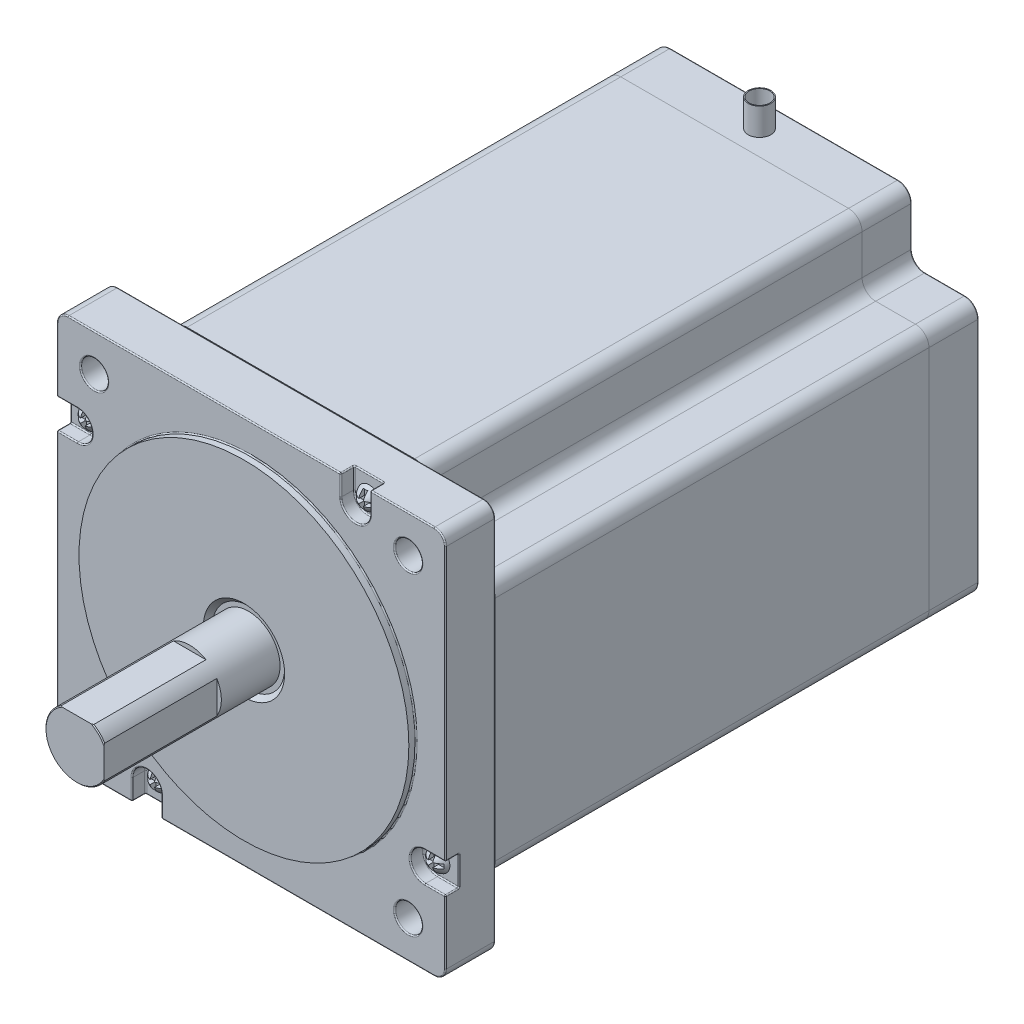
SolidWorks part; units mm, degrees
ref_plane "Front Plane" through (0, 0, 0) normal (0, 0, 1) x (1, 0, 0)
ref_plane "Top Plane" through (0, 0, 0) normal (0, 1, 0) x (1, 0, 0)
ref_plane "Right Plane" through (0, 0, 0) normal (1, 0, 0) x (0, 0, -1)
sketch "Sketch1" plane through (0, 0, 0) normal (0, 0, 1) x (1, 0, 0)
  line L0 (-43, 28.2) -> (-28.2, 28.2)
  line L1 (-28.2, 43) -> (28.2, 43)
  line L2 (-43, 28.2) -> (-43, -28.2)
  line L3 (-28.2, -43) -> (28.2, -43)
  line L4 (43, 28.2) -> (43, -28.2)
  line L7 (-28.2, 28.2) -> (-28.2, 43)
  line L8 (28.2, 43) -> (28.2, 28.2)
  line L9 (28.2, 28.2) -> (43, 28.2)
  line L10 (43, -28.2) -> (28.2, -28.2)
  line L11 (28.2, -28.2) -> (28.2, -43)
  line L12 (-28.2, -43) -> (-28.2, -28.2)
  line L13 (-28.2, -28.2) -> (-43, -28.2)
  line L14 (0, -40.6029) -> (0, 56.0394) construction
  line L15 (-73.473, 0) -> (63.7944, 0) construction
  circle A0 centre (-38.44, 23.1) radius 1.25
  circle A1 centre (0, 0) radius 8.1575 construction
  circle A2 centre (23.1, 38.44) radius 1.25
  circle A3 centre (38.44, -23.1) radius 1.25
  circle A4 centre (-23.1, -38.44) radius 1.25
  point P0 (0, 0)
  point P32 (0, 0)
  dimension "D3" = 2.5
  dimension "D4" = 4.56
  dimension "D5" = 19.9
  dimension "D6" = 4
  dimension "D1" = 43
  dimension "D2" = 86
  dimension "D7" = 43
  dimension "D8" = 14.8
  dimension "D9" = 14.8
extrude "Boss-Extrude1" add sketch "Sketch1" along normal mid plane 96
fillet "Fillet1" radius 3 12 edges at (43, -28.2, 0) (28.2, -28.2, 0) (28.2, -43, 0) (-28.2, -43, 0) (-28.2, -28.2, 0) (-43, -28.2, 0) (-43, 28.2, 0) (-28.2, 28.2, 0) (-28.2, 43, 0) (43, 28.2, 0) (28.2, 28.2, 0) (28.2, 43, 0)
sketch "Sketch2" plane through (0, 0, -48) normal (0, 0, -1) x (-1, 0, 0)
  line L12 (-43, 25.2) -> (-43, -25.2)
  line L13 (-40, -28.2) -> (-31.2, -28.2)
  line L14 (-28.2, -31.2) -> (-28.2, -40)
  line L15 (-25.2, -43) -> (25.2, -43)
  line L16 (28.2, -40) -> (28.2, -31.2)
  line L17 (31.2, -28.2) -> (40, -28.2)
  line L18 (43, -25.2) -> (43, 25.2)
  line L19 (40, 28.2) -> (31.2, 28.2)
  line L20 (28.2, 31.2) -> (28.2, 40)
  line L21 (25.2, 43) -> (-25.2, 43)
  line L22 (-28.2, 40) -> (-28.2, 31.2)
  line L23 (-31.2, 28.2) -> (-40, 28.2)
  line L24 (-43, 25.2) -> (-43, -25.2)
  line L25 (-40, -28.2) -> (-31.2, -28.2)
  line L26 (-28.2, -31.2) -> (-28.2, -40)
  line L27 (-25.2, -43) -> (25.2, -43)
  line L28 (28.2, -40) -> (28.2, -31.2)
  line L29 (31.2, -28.2) -> (40, -28.2)
  line L30 (43, -25.2) -> (43, 25.2)
  line L31 (40, 28.2) -> (31.2, 28.2)
  line L32 (28.2, 31.2) -> (28.2, 40)
  line L33 (25.2, 43) -> (-25.2, 43)
  line L34 (-28.2, 40) -> (-28.2, 31.2)
  line L35 (-31.2, 28.2) -> (-40, 28.2)
  circle A0 centre (38.44, 23.1) radius 1.25 construction
  circle A1 centre (-23.1, 38.44) radius 1.25 construction
  circle A2 centre (-38.44, -23.1) radius 1.25 construction
  circle A3 centre (23.1, -38.44) radius 1.25 construction
  circle A4 centre (38.44, 23.1) radius 1.25
  circle A5 centre (23.1, -38.44) radius 1.25
  circle A6 centre (-38.44, -23.1) radius 1.25
  circle A7 centre (-23.1, 38.44) radius 1.25
  arc A20 (-43, -25.2) -> (-40, -28.2) centre (-40, -25.2) ccw
  arc A21 (-28.2, -31.2) -> (-31.2, -28.2) centre (-31.2, -31.2) ccw
  arc A22 (-28.2, -40) -> (-25.2, -43) centre (-25.2, -40) ccw
  arc A23 (25.2, -43) -> (28.2, -40) centre (25.2, -40) ccw
  arc A24 (31.2, -28.2) -> (28.2, -31.2) centre (31.2, -31.2) ccw
  arc A25 (40, -28.2) -> (43, -25.2) centre (40, -25.2) ccw
  arc A26 (43, 25.2) -> (40, 28.2) centre (40, 25.2) ccw
  arc A27 (28.2, 31.2) -> (31.2, 28.2) centre (31.2, 31.2) ccw
  arc A28 (28.2, 40) -> (25.2, 43) centre (25.2, 40) ccw
  arc A29 (-25.2, 43) -> (-28.2, 40) centre (-25.2, 40) ccw
  arc A30 (-31.2, 28.2) -> (-28.2, 31.2) centre (-31.2, 31.2) ccw
  arc A31 (-40, 28.2) -> (-43, 25.2) centre (-40, 25.2) ccw
  arc A32 (-43, -25.2) -> (-40, -28.2) centre (-40, -25.2) ccw
  arc A33 (-28.2, -31.2) -> (-31.2, -28.2) centre (-31.2, -31.2) ccw
  arc A34 (-28.2, -40) -> (-25.2, -43) centre (-25.2, -40) ccw
  arc A35 (25.2, -43) -> (28.2, -40) centre (25.2, -40) ccw
  arc A36 (31.2, -28.2) -> (28.2, -31.2) centre (31.2, -31.2) ccw
  arc A37 (40, -28.2) -> (43, -25.2) centre (40, -25.2) ccw
  arc A38 (43, 25.2) -> (40, 28.2) centre (40, 25.2) ccw
  arc A39 (28.2, 31.2) -> (31.2, 28.2) centre (31.2, 31.2) ccw
  arc A40 (28.2, 40) -> (25.2, 43) centre (25.2, 40) ccw
  arc A41 (-25.2, 43) -> (-28.2, 40) centre (-25.2, 40) ccw
  arc A42 (-31.2, 28.2) -> (-28.2, 31.2) centre (-31.2, 31.2) ccw
  arc A43 (-40, 28.2) -> (-43, 25.2) centre (-40, 25.2) ccw
  dimension "D1" = 0
extrude "Boss-Extrude2" add sketch "Sketch2" along normal blind 11 separate body
sketch "Sketch4" plane through (0, 0, 48) normal (0, 0, 1) x (1, 0, 0)
  line L1 (-43, 43) -> (43, 43)
  line L2 (-43, 43) -> (-43, -43)
  line L3 (-43, -43) -> (43, -43)
  line L4 (43, 43) -> (43, -43)
  line L5 (-43, 43) -> (43, -43) construction
  line L6 (-43, -43) -> (43, 43) construction
  circle A0 centre (-23.1, -38.44) radius 1.25 construction
  circle A1 centre (38.44, -23.1) radius 1.25 construction
  circle A2 centre (23.1, 38.44) radius 1.25 construction
  circle A3 centre (-38.44, 23.1) radius 1.25 construction
  circle A4 centre (-23.1, -38.44) radius 1.25
  circle A5 centre (38.44, -23.1) radius 1.25
  circle A6 centre (23.1, 38.44) radius 1.25
  circle A7 centre (-38.44, 23.1) radius 1.25
  point P0 (0, 0)
  dimension "D1" = 86
  dimension "D2" = 86
extrude "Boss-Extrude3" add sketch "Sketch4" along normal blind 11 separate body
fillet "Fillet2" radius 2.5 4 edges at (-43, -43, 53.5) (43, -43, 53.5) (43, 43, 53.5) (-43, 43, 53.5)
sketch "Sketch5" plane through (0, 0, 59) normal (0, 0, 1) x (1, 0, 0)
  line L0 (-38.44, 26.35) -> (-43, 26.35)
  line L1 (-43, 40.5) -> (-43, -40.5) construction
  line L2 (-43, 26.35) -> (-43, 19.85)
  line L3 (-43, 19.85) -> (-38.44, 19.85)
  line L4 (26.35, 38.44) -> (26.35, 43)
  line L5 (26.35, 43) -> (19.85, 43)
  line L6 (19.85, 43) -> (19.85, 38.44)
  line L7 (38.44, -26.35) -> (43, -26.35)
  line L8 (43, -26.35) -> (43, -19.85)
  line L9 (43, -19.85) -> (38.44, -19.85)
  line L10 (-26.35, -38.44) -> (-26.35, -43)
  line L11 (-26.35, -43) -> (-19.85, -43)
  line L12 (-19.85, -43) -> (-19.85, -38.44)
  arc A0 (-38.44, 19.85) -> (-38.44, 26.35) centre (-38.44, 23.1) ccw
  circle A1 centre (0, 0) radius 8.2773 construction
  arc A2 (19.85, 38.44) -> (26.35, 38.44) centre (23.1, 38.44) ccw
  circle A3 centre (0, 0) radius 8.2773 construction
  arc A4 (38.44, -19.85) -> (38.44, -26.35) centre (38.44, -23.1) ccw
  circle A5 centre (0, 0) radius 8.2773 construction
  arc A6 (-19.85, -38.44) -> (-26.35, -38.44) centre (-23.1, -38.44) ccw
  circle A7 centre (0, 0) radius 8.2773 construction
  point P32 (0, 0)
  dimension "D1" = 6.5
  dimension "D2" = 4
extrude "Cut-Extrude1" cut sketch "Sketch5" against normal blind 3
sketch "Sketch6" plane through (0, 0, 59) normal (0, 0, 1) x (1, 0, 0)
  line L2 (0, 0) -> (0, 46.7465) construction
  line L3 (0, 0) -> (-44.6638, 0) construction
  circle A0 centre (-34.75, 34.75) radius 3
  circle A1 centre (0, 0) radius 7.1558 construction
  circle A2 centre (34.75, 34.75) radius 3
  circle A3 centre (0, 0) radius 7.1558 construction
  circle A4 centre (34.75, -34.75) radius 3
  circle A5 centre (0, 0) radius 7.1558 construction
  circle A6 centre (-34.75, -34.75) radius 3
  circle A7 centre (0, 0) radius 7.1558 construction
  point P20 (0, 0)
  dimension "D1" = 6
  dimension "D3" = 34.75
  dimension "D2" = 34.75
  dimension "D4" = 4
extrude "Cut-Extrude2" cut sketch "Sketch6" against normal up to surface (11 mm away) up to face at (0, 0, 48)
sketch "Sketch7" plane through (0, 0, 59) normal (0, 0, 1) x (1, 0, 0)
  circle A0 centre (0, 0) radius 36.5
  dimension "D1" = 73
extrude "Boss-Extrude4" add sketch "Sketch7" along normal blind 1.6
sketch "Sketch8" plane through (0, 0, 60.6) normal (0, 0, 1) x (1, 0, 0)
  circle A0 centre (0, 0) radius 7 construction
  circle A1 centre (0, 0) radius 8
  dimension "D1" = 14
  dimension "D2" = 16
extrude "Cut-Extrude3" cut sketch "Sketch8" against normal through all
chamfer "Chamfer1" distance 1 angle 45 1 edges at (8, 0, -59)
chamfer "Chamfer2" distance 1 angle 45 1 edges at (8, 0, 60.6)
ref_plane "Plane1" through (0, 0, 59.6) normal (0, 0, 1) x (1, 0, 0)
sketch "Sketch9" plane through (0, 0, 59.6) normal (0, 0, 1) x (1, 0, 0)
  circle A0 centre (0, 0) radius 7
  circle A1 centre (0, 0) radius 8 construction
  circle A2 centre (0, 0) radius 8
  dimension "D1" = 14
extrude "Boss-Extrude5" add sketch "Sketch9" against normal blind 57.5 separate body
ref_plane "Plane2" through (0, 0, 80) normal (0, 0, 1) x (1, 0, 0)
sketch "Sketch10" plane through (0, 0, 80) normal (0, 0, 1) x (1, 0, 0)
  circle A0 centre (0, 0) radius 7 construction
  circle A1 centre (0, 0) radius 7
extrude "Boss-Extrude6" add sketch "Sketch10" against normal offset from surface 15 and the other way blind 17.6 separate body up to face at (-9, 0, -59)
ref_plane "Plane3" through (-38.47, 0, 0) normal (-1, 0, 0) x (0, 0, 1)
sketch "Sketch11" plane through (-38.47, 0, 0) normal (-1, 0, 0) x (0, 0, 1)
  line L0 (59, 23.1) -> (-34.8778, 23.1) construction
  line L1 (59, 19.85) -> (59, 26.35) construction
  line L2 (58, 23.1) -> (56, 23.1)
  line L3 (56, 26.35) -> (56, 19.85) construction
  line L4 (56, 23.1) -> (56, 25.6)
  arc A0 (56, 25.6) -> (58, 23.1) centre (54.7392, 22.5413) cw
  dimension "D1" = 2.5
  dimension "D2" = 2
sketch "Sketch16" plane through (0, 0, 80) normal (0, 0, 1) x (1, 0, 0)
  circle A0 centre (0, 0) radius 9.8427 construction
chamfer "Chamfer4" distance 0.2 angle 45 1 edges at (7, 0, 97.6)
chamfer "Chamfer5" distance 0.2 angle 45 1 edges at (-7, 0, -44)
fillet "Fillet3" radius 0.25 29 edges at (23.1, 35.19, 59) (26.35, 40.72, 59) (33.425, 43, 59) (42.2678, 42.2678, 59) (43, 10.325, 59) (40.72, -19.85, 59) (35.19, -23.1, 59) (40.72, -26.35, 59) (43, -33.425, 59) (42.2678, -42.2678, 59) (10.325, -43, 59) (-19.85, -40.72, 59) (-23.1, -35.19, 59) (-26.35, -40.72, 59) (-33.425, -43, 59) (-42.2678, -42.2678, 59) (-43, -10.325, 59) (-40.72, 19.85, 59) (-35.19, 23.1, 59) (-40.72, 26.35, 59) (-43, 33.425, 59) (-42.2678, 42.2678, 59) (-10.325, 43, 59) (19.85, 40.72, 59) (-31.75, -34.75, 59) (37.75, -34.75, 59) (37.75, 34.75, 59) (-31.75, 34.75, 59) (36.5, 0, 59)
fillet "Fillet4" radius 0.25 35 edges at (-26.4232, -42.9268, 58.9268) (19.7768, 42.9268, 58.9268) (26.4232, 42.9268, 58.9268) (-42.9268, 19.7768, 58.9268) (-42.9268, 26.4232, 58.9268) (-26.35, -43, 57.375) (42.9268, -19.7768, 58.9268) (42.9268, -26.4232, 58.9268) (19.85, 43, 57.375) (26.35, 43, 57.375) (-43, 19.85, 57.375) (-43, 26.35, 57.375) (-23.1, -43, 56) (43, -19.85, 57.375) (43, -26.35, 57.375) (-26.35, -40.72, 56) (-23.1, -35.19, 56) (-19.7768, -42.9268, 58.9268) (19.85, 40.72, 56) (23.1, 43, 56) (26.35, 40.72, 56) (23.1, 35.19, 56) (24.35, 38.44, 56) (-40.72, 19.85, 56) (-43, 23.1, 56) (-40.72, 26.35, 56) (-35.19, 23.1, 56) (-37.19, 23.1, 56) (-19.85, -40.72, 56) (-19.85, -43, 57.375) (40.72, -19.85, 56) (43, -23.1, 56) (40.72, -26.35, 56) (35.19, -23.1, 56) (39.69, -23.1, 56)
fillet "Fillet5" radius 0.25 29 edges at (21.85, 38.44, -59) (-24.35, -38.44, -59) (35.6, 28.2, -59) (29.0787, 29.0787, -59) (28.2, 35.6, -59) (27.3213, 42.1213, -59) (0, 43, -59) (-27.3213, 42.1213, -59) (-28.2, 35.6, -59) (-29.0787, 29.0787, -59) (-35.6, 28.2, -59) (-42.1213, 27.3213, -59) (-43, 0, -59) (-42.1213, -27.3213, -59) (-35.6, -28.2, -59) (-29.0787, -29.0787, -59) (-28.2, -35.6, -59) (-27.3213, -42.1213, -59) (0, -43, -59) (27.3213, -42.1213, -59) (28.2, -35.6, -59) (29.0787, -29.0787, -59) (35.6, -28.2, -59) (42.1213, -27.3213, -59) (43, 0, -59) (42.1213, 27.3213, -59) (-39.69, 23.1, -59) (37.19, -23.1, -59) (-9, 0, -59)
fillet "Fillet6" radius 0.25 17 edges at (-37.19, 23.1, 48) (24.35, 38.44, 48) (39.69, -23.1, 48) (-21.85, -38.44, 48) (42.2678, -42.2678, 48) (43, 0, 48) (42.2678, 42.2678, 48) (0, 43, 48) (-42.2678, 42.2678, 48) (-43, 0, 48) (-42.2678, -42.2678, 48) (0, -43, 48) (-31.75, -34.75, 48) (37.75, -34.75, 48) (37.75, 34.75, 48) (-31.75, 34.75, 48) (8, 0, 48)
sketch "Sketch18" plane through (0, 43, 0) normal (0, 1, 0) x (1, 0, 0)
  line L0 (-13.2998, 53.5) -> (11.7015, 53.5) construction
  line L1 (-25.2, 48) -> (25.2, 48) construction
  line L2 (-25.2, 59) -> (25.2, 59) construction
  circle A0 centre (0, 53.5) radius 2.5
  circle A1 centre (0, 53.5) radius 2.3
  dimension "D1" = 5
  dimension "D2" = 0.2
extrude "Boss-Extrude8" add sketch "Sketch18" along normal blind 6 separate body
sketch "Sketch24" plane through (0, 0, 97.6) normal (0, 0, 1) x (1, 0, 0)
  line L1 (-13.5328, 14.1729) -> (10.8212, 14.1729)
  line L2 (-13.5328, 14.1729) -> (-13.5328, 6)
  line L3 (-13.5328, 6) -> (10.8212, 6)
  line L4 (10.8212, 14.1729) -> (10.8212, 6)
  line L5 (6, 4.6554) -> (10.2236, 4.6554)
  line L6 (6, 4.6554) -> (6, -5.5469)
  line L7 (6, -5.5469) -> (10.2236, -5.5469)
  line L8 (10.2236, 4.6554) -> (10.2236, -5.5469)
  dimension "D1" = 6
  dimension "D2" = 6
extrude "Cut-Extrude4" cut sketch "Sketch24" against normal blind 25
revolve "Revolve1" add sketch "Sketch11" angle 360 about L0
sketch "Sketch25" plane through (0, 0, 59) normal (0, 0, 1) x (1, 0, 0)
  line L0 (-37.97, 23.1) -> (-35.97, 23.1) construction
  line L1 (-38.47, 23.1) -> (-38.47, 25.6) construction
  line L2 (-37.97, 22.6) -> (-37.97, 21.1)
  line L3 (-40.47, 23.6) -> (-38.97, 23.6)
  line L4 (-40.47, 23.6) -> (-40.47, 22.6)
  line L5 (-40.47, 22.6) -> (-38.97, 22.6)
  line L6 (-36.47, 23.6) -> (-36.47, 22.6)
  line L7 (-40.47, 23.6) -> (-36.47, 22.6) construction
  line L8 (-40.47, 22.6) -> (-36.47, 23.6) construction
  line L9 (-38.97, 25.1) -> (-37.97, 25.1)
  line L10 (-38.97, 25.1) -> (-38.97, 23.6)
  line L11 (-38.97, 21.1) -> (-37.97, 21.1)
  line L12 (-37.97, 25.1) -> (-37.97, 23.6)
  line L13 (-38.97, 25.1) -> (-37.97, 21.1) construction
  line L14 (-38.97, 21.1) -> (-37.97, 25.1) construction
  line L15 (-38.97, 22.6) -> (-38.97, 21.1)
  line L16 (-37.97, 22.6) -> (-36.47, 22.6)
  line L17 (-37.97, 23.6) -> (-36.47, 23.6)
  line L18 (-41.8676, 23.1) -> (-33.6892, 23.1) construction
  circle A0 centre (-38.47, 23.1) radius 2.5 construction
  point P22 (-36.47, 23.1)
  dimension "D1" = 1
  dimension "D2" = 1
  dimension "D3" = 2
  dimension "D4" = 2
  dimension "D5" = 1.5
extrude "Cut-Extrude5" cut sketch "Sketch25" against normal blind 2.5
pattern_circular "CirPattern1" count 4 over 360 about axis through (0, 0, 60.6) along (0, 0, 1) of "Revolve1", "Cut-Extrude5"
